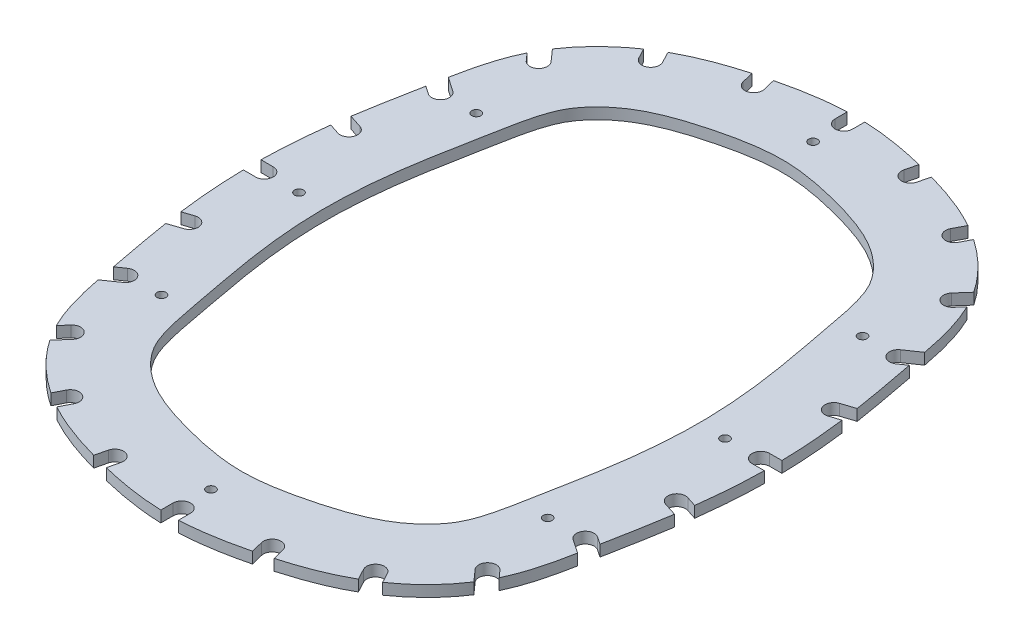
SolidWorks part; units mm, degrees
ref_plane "Front Plane" through (0, 0, 0) normal (0, 0, 1) x (1, 0, 0)
ref_plane "Top Plane" through (0, 0, 0) normal (0, 1, 0) x (1, 0, 0)
ref_plane "Right Plane" through (0, 0, 0) normal (1, 0, 0) x (0, 0, -1)
sketch "MainControlPoints" plane through (0, 0, 0) normal (0, 1, 0) x (1, 0, 0)
  line L1 (0, 188.5) -> (0, 0) construction
  line L2 (-44.5, 181.8105) -> (44.5, 181.8105) construction
  line L9 (-141, 0) -> (141, 0) construction
  line L10 (-86.25, 165.0195) -> (86.25, 165.0195) construction
  line L11 (-117.5, 132.6399) -> (117.5, 132.6399) construction
  line L12 (-130, 89.4108) -> (130, 89.4108) construction
  line L13 (-137.75, 45.0832) -> (137.75, 45.0832) construction
  spline S0 degree 3 poles (-44.8235, 182.8439) (0, 191.3281) (44.8235, 182.8439) (87.706, 168.1591) (121.8523, 134.6364) (129.8847, 89.1344) (138.6218, 45.2258) (142.1917, 0) (138.6218, -45.2258) (129.8847, -89.1344) (121.8523, -134.6364) (87.706, -168.1591) (44.8235, -182.8439) (0, -191.3281) (-44.8235, -182.8439) (-87.706, -168.1591) (-121.8523, -134.6364) (-129.8847, -89.1344) (-138.6218, -45.2258) (-142.1917, 0) (-138.6218, 45.2258) (-129.8847, 89.1344) (-121.8523, 134.6364) (-87.706, 168.1591) (-44.8235, 182.8439) (0, 191.3281) (44.8235, 182.8439) knots -0.124907 -0.083272 -0.041636 0 0.041636 0.083272 0.124907 0.166543 0.208179 0.25 0.291821 0.333457 0.375093 0.416728 0.458364 0.5 0.541636 0.583272 0.624907 0.666543 0.708179 0.75 0.791821 0.833457 0.875093 0.916728 0.958364 1 1.041636 1.083272 1.124907 only from (0, 188.5) to (0, 188.5)
  point P4 (0, 181.8105)
  point P7 (0, 0)
  point P8 (141, 0)
  point P9 (-141, 0)
  point P11 (44.5, 181.8105)
  point P14 (86.25, 165.0195)
  point P15 (0, 165.0195)
  point P16 (117.5, 132.6399)
  point P17 (130, 89.4108)
  point P18 (-44.5, 181.8105)
  point P19 (-86.25, 165.0195)
  point P20 (-117.5, 132.6399)
  point P23 (0, 132.6399)
  point P24 (137.75, 45.0832)
  point P25 (-130, 89.4108)
  point P26 (-137.75, 45.0832)
  point P27 (0, 188.5)
  point P30 (0, 89.4108)
  point P33 (0, 45.0832)
  point P34 (137.75, -45.0832)
  point P35 (130, -89.4108)
  point P36 (117.5, -132.6399)
  point P37 (86.25, -165.0195)
  point P38 (44.5, -181.8105)
  point P39 (0, -188.5)
  point P40 (-44.5, -181.8105)
  point P41 (-86.25, -165.0195)
  point P42 (-117.5, -132.6399)
  point P43 (-130, -89.4108)
  point P44 (-137.75, -45.0832)
  dimension "D3" = 282
  dimension "D2" = 188.5
  dimension "D5" = 45
  dimension "D6" = 45
  dimension "D1" = 89
  dimension "D4" = 172.5
  dimension "D7" = 45
  dimension "D8" = 235
  dimension "D9" = 45
  dimension "D10" = 260
  dimension "D11" = 45
  dimension "D12" = 275.5
ref_axis "Axis1" through (0, 0, -188.5) along (0, 1, 0)
ref_axis "Axis2" through (44.5, 0, -181.8105) along (0, 1, 0)
ref_axis "Axis3" through (86.25, 0, -165.0195) along (0, 1, 0)
ref_axis "Axis4" through (117.5, 0, -132.6399) along (0, 1, 0)
ref_axis "Axis5" through (130, 0, -89.4108) along (0, 1, 0)
ref_axis "Axis6" through (137.75, 0, -45.0832) along (0, 1, 0)
ref_axis "Axis7" through (141, 0, 0) along (0, 1, 0)
ref_axis "Axis8" through (137.75, 0, 45.0832) along (0, 1, 0)
ref_axis "Axis9" through (130, 0, 89.4108) along (0, 1, 0)
ref_axis "Axis10" through (117.5, 0, 132.6399) along (0, 1, 0)
ref_axis "Axis11" through (86.25, 0, 165.0195) along (0, 1, 0)
ref_axis "Axis12" through (44.5, 0, 181.8105) along (0, 1, 0)
ref_axis "Axis13" through (0, 0, 188.5) along (0, 1, 0)
ref_axis "Axis14" through (-44.5, 0, 181.8105) along (0, 1, 0)
ref_axis "Axis15" through (-86.25, 0, 165.0195) along (0, 1, 0)
ref_axis "Axis16" through (-117.5, 0, 132.6399) along (0, 1, 0)
ref_axis "Axis17" through (-130, 0, 89.4108) along (0, 1, 0)
ref_axis "Axis18" through (-137.75, 0, 45.0832) along (0, 1, 0)
ref_axis "Axis19" through (-141, 0, 0) along (0, 1, 0)
ref_axis "Axis20" through (-137.75, 0, -45.0832) along (0, 1, 0)
ref_axis "Axis21" through (-130, 0, -89.4108) along (0, 1, 0)
ref_axis "Axis22" through (-117.5, 0, -132.6399) along (0, 1, 0)
ref_axis "Axis23" through (-86.25, 0, -165.0195) along (0, 1, 0)
ref_axis "Axis24" through (-44.5, 0, -181.8105) along (0, 1, 0)
sketch "Sketch3" plane through (0, 0, 0) normal (0, 1, 0) x (1, 0, 0)
  spline S2 degree 3 poles (44.8235, 182.8439) (0, 191.3281) (-44.8235, 182.8439) (-87.706, 168.1591) (-121.8523, 134.6364) (-129.8847, 89.1344) (-138.6218, 45.2258) (-142.1917, 0) (-138.6218, -45.2258) (-129.8847, -89.1344) (-121.8523, -134.6364) (-87.706, -168.1591) (-44.8235, -182.8439) (0, -191.3281) (44.8235, -182.8439) (87.706, -168.1591) (121.8523, -134.6364) (129.8847, -89.1344) (138.6218, -45.2258) (142.1917, 0) (138.6218, 45.2258) (129.8847, 89.1344) (121.8523, 134.6364) (87.706, 168.1591) (44.8235, 182.8439) (0, 191.3281) (-44.8235, 182.8439) knots -0.124907 -0.083272 -0.041636 0 0.041636 0.083272 0.124907 0.166543 0.208179 0.25 0.291821 0.333457 0.375093 0.416728 0.458364 0.5 0.541636 0.583272 0.624907 0.666543 0.708179 0.75 0.791821 0.833457 0.875093 0.916728 0.958364 1 1.041636 1.083272 1.124907 only from (0, 188.5) to (0, 188.5)
  spline S3 degree 3 poles (44.8235, 182.8439) (0, 191.3281) (-44.8235, 182.8439) (-87.706, 168.1591) (-121.8523, 134.6364) (-129.8847, 89.1344) (-138.6218, 45.2258) (-142.1917, 0) (-138.6218, -45.2258) (-129.8847, -89.1344) (-121.8523, -134.6364) (-87.706, -168.1591) (-44.8235, -182.8439) (0, -191.3281) (44.8235, -182.8439) (87.706, -168.1591) (121.8523, -134.6364) (129.8847, -89.1344) (138.6218, -45.2258) (142.1917, 0) (138.6218, 45.2258) (129.8847, 89.1344) (121.8523, 134.6364) (87.706, 168.1591) (44.8235, 182.8439) (0, 191.3281) (-44.8235, 182.8439) knots -0.124907 -0.083272 -0.041636 0 0.041636 0.083272 0.124907 0.166543 0.208179 0.25 0.291821 0.333457 0.375093 0.416728 0.458364 0.5 0.541636 0.583272 0.624907 0.666543 0.708179 0.75 0.791821 0.833457 0.875093 0.916728 0.958364 1 1.041636 1.083272 1.124907 only from (0, 188.5) to (0, 188.5)
  dimension "D1" = 0
extrude "MainBody" add sketch "Sketch3" along normal blind 6.35
sketch "Sketch13" plane through (0, 6.35, 0) normal (0, 1, 0) x (1, 0, 0)
  spline S2 degree 3 poles (-0.0923, -195.5) (5.9061, -195.5) (11.7392, -195.085) (23.2981, -193.6453) (29.0237, -192.6199) (37.5559, -190.7615) (40.3905, -190.0886) (46.0447, -188.657) (48.8649, -187.9023) (53.0829, -186.6998) (54.4867, -186.2866) (57.2893, -185.4316) (58.6882, -184.9896) (62.8604, -183.6197) (65.6138, -182.6462) (73.7714, -179.5048) (79.0728, -177.1157) (86.7462, -172.933) (89.2575, -171.4385) (92.9463, -169.029) (94.1653, -168.1965) (96.5575, -166.4889) (97.7326, -165.6128) (101.1944, -162.9177) (103.4182, -161.032) (107.6923, -157.0772) (109.7427, -155.0081) (112.678, -151.7562) (113.633, -150.6474) (115.0284, -148.9451) (115.4873, -148.3711) (116.3925, -147.2097) (116.8393, -146.6213) (119.0306, -143.6582) (120.6466, -141.2209) (123.5916, -136.206) (124.9153, -133.6259) (127.2923, -128.3337) (128.3485, -125.623) (129.7723, -121.4785) (130.2202, -120.084) (131.0691, -117.272) (131.4694, -115.8571) (132.6042, -111.6095) (133.2755, -108.7656) (134.5145, -103.0626) (135.0819, -100.2036) (136.1775, -94.48) (136.707, -91.6156) (138.3251, -83.0265) (139.4215, -77.303) (141.5293, -65.8438) (142.5403, -60.108) (143.9035, -51.4821) (144.3323, -48.6031) (145.1247, -42.8358) (145.4885, -39.9475) (147.1362, -25.4811) (147.9101, -13.8294) (148.003, -0.6092) (148.0024, 0.8623) (147.9792, 3.8019) (147.9568, 5.2701) (147.8578, 9.6699) (147.7498, 12.5969) (147.3068, 21.3604) (146.8533, 27.1792) (145.6651, 38.7754) (144.9284, 44.5524) (143.2126, 56.0705) (142.2389, 61.8124) (140.1775, 73.2794) (139.0901, 79.0044) (137.4645, 87.5929) (136.9262, 90.4562) (135.8531, 96.1835) (135.3122, 99.0464) (133.5786, 107.6189) (132.2779, 113.3124) (130.1353, 120.3529) (129.6824, 121.7514) (128.7233, 124.5187) (128.2169, 125.8886) (126.6073, 129.9525) (125.4138, 132.6004) (122.7385, 137.7496) (121.2544, 140.2496) (118.8215, 143.8945) (117.9761, 145.0919) (116.2177, 147.4523) (115.3033, 148.6168) (112.4942, 152.0199) (110.5242, 154.1827) (106.4077, 158.3162) (104.2612, 160.2869) (99.8013, 164.0465) (97.4878, 165.8355) (93.8939, 168.384) (92.6724, 169.2128) (90.2027, 170.8151) (88.9554, 171.5879) (82.6598, 175.3171) (77.4348, 177.8708) (66.7035, 182.3362) (61.1969, 184.2476) (54.1978, 186.3725) (52.791, 186.7846) (49.9736, 187.5842) (48.5634, 187.9716) (44.3294, 189.1029) (41.5021, 189.818) (33.0032, 191.8167) (27.3144, 192.953) (15.8708, 194.6608) (10.1162, 195.2328) (1.4182, 195.5241) (-1.4925, 195.5238) (-7.3372, 195.3237) (-10.2708, 195.1267) (-14.6866, 194.6996) (-16.1609, 194.5352) (-19.0943, 194.1679) (-20.556, 193.9647) (-24.9277, 193.3015) (-27.824, 192.7881) (-36.4681, 191.071) (-42.1715, 189.6926) (-53.5026, 186.6371) (-59.1262, 184.9441) (-66.0624, 182.4605) (-67.445, 181.9454) (-70.1997, 180.8739) (-71.5737, 180.3168) (-75.6639, 178.5832) (-78.3432, 177.3468) (-83.5935, 174.6901) (-86.1644, 173.2698) (-91.1858, 170.2243) (-93.6357, 168.5985) (-97.2169, 166.0005) (-98.395, 165.108) (-100.7189, 163.2682) (-101.8655, 162.32) (-105.2234, 159.4186) (-107.3637, 157.4004) (-111.4418, 153.191) (-113.3796, 150.9998) (-117.0378, 146.4319) (-118.7583, 144.0551) (-121.1568, 140.3344) (-121.9259, 139.0681) (-123.0304, 137.1268) (-123.3898, 136.4736) (-124.087, 135.1618) (-124.4255, 134.5022) (-126.0692, 131.1868) (-127.2294, 128.4785) (-130.3408, 120.2205) (-131.9223, 114.5371) (-134.5909, 102.9918) (-135.6643, 97.1921) (-137.8355, 85.5987) (-138.9477, 79.8043) (-141.1029, 68.2094) (-142.1451, 62.4088) (-143.5618, 53.6948) (-144.0097, 50.788) (-144.8419, 44.9686) (-145.2255, 42.056) (-146.97, 27.4776) (-147.815, 15.7657) (-148.0521, -1.8942) (-147.9538, -7.7967) (-147.4225, -19.6316) (-146.9909, -25.5639) (-146.1143, -34.4827) (-145.7838, -37.4592) (-145.0527, -43.3941) (-144.6515, -46.3556) (-143.3516, -55.2244) (-142.36, -61.1163) (-140.253, -72.8796) (-139.1381, -78.7512) (-137.4708, -87.5593) (-136.9189, -90.496) (-135.8181, -96.3698) (-135.2627, -99.3053) (-133.4794, -108.0788) (-132.1352, -113.8842) (-129.4893, -122.4151) (-128.5024, -125.2292) (-126.8117, -129.3912) (-126.2131, -130.7686) (-125.2553, -132.818) (-124.9263, -133.498) (-124.2516, -134.843) (-123.9056, -135.5092) (-122.1306, -138.8075) (-120.5688, -141.343) (-117.1925, -146.2303) (-115.378, -148.582) (-111.5149, -153.1153) (-109.4647, -155.2983) (-105.1449, -159.494) (-102.9036, -161.4797) (-95.9543, -167.1259) (-91.0211, -170.4758) (-84.4967, -174.1698) (-83.1716, -174.8856) (-80.5028, -176.2632) (-79.1594, -176.925) (-75.1047, -178.8358) (-72.3686, -180.0105) (-64.0786, -183.2871) (-58.4429, -185.1422) (-49.8888, -187.6214) (-47.0211, -188.3984) (-41.2605, -189.8765) (-38.3664, -190.5739) (-32.5429, -191.862) (-29.6099, -192.4531) (-23.735, -193.4975) (-20.7901, -193.9515) (-14.8831, -194.699) (-11.9208, -194.9924) (-7.4624, -195.2928) (-5.9738, -195.3696) (-3.7367, -195.4473) (-2.6172, -195.4768) (-1.3092, -195.4942) (-0.6548, -195.4985) (-0.3742, -195.4995) (-0.1871, -195.4999) (-0.0923, -195.5) (5.9061, -195.5) (11.7392, -195.085) knots -0.000244 -0.000244 0 0 0.015625 0.015625 0.03125 0.03125 0.039063 0.039063 0.046875 0.046875 0.050781 0.050781 0.054688 0.054688 0.0625 0.0625 0.078125 0.078125 0.085938 0.085938 0.089844 0.089844 0.09375 0.09375 0.101563 0.101563 0.109375 0.109375 0.113281 0.113281 0.115234 0.115234 0.117188 0.117188 0.125 0.125 0.132813 0.132813 0.140625 0.140625 0.144531 0.144531 0.148438 0.148438 0.15625 0.15625 0.164063 0.164063 0.171875 0.171875 0.1875 0.1875 0.203125 0.203125 0.210938 0.210938 0.21875 0.21875 0.25 0.25 0.253906 0.253906 0.257813 0.257813 0.265625 0.265625 0.28125 0.28125 0.296875 0.296875 0.3125 0.3125 0.328125 0.328125 0.335938 0.335938 0.34375 0.34375 0.359375 0.359375 0.363281 0.363281 0.367188 0.367188 0.375 0.375 0.382813 0.382813 0.386719 0.386719 0.390625 0.390625 0.398438 0.398438 0.40625 0.40625 0.414063 0.414063 0.417969 0.417969 0.421875 0.421875 0.4375 0.4375 0.453125 0.453125 0.457031 0.457031 0.460938 0.460938 0.46875 0.46875 0.484375 0.484375 0.5 0.5 0.507813 0.507813 0.515625 0.515625 0.519531 0.519531 0.523438 0.523438 0.53125 0.53125 0.546875 0.546875 0.5625 0.5625 0.566406 0.566406 0.570313 0.570313 0.578125 0.578125 0.585938 0.585938 0.59375 0.59375 0.597656 0.597656 0.601563 0.601563 0.609375 0.609375 0.617188 0.617188 0.625 0.625 0.628906 0.628906 0.630859 0.630859 0.632813 0.632813 0.640625 0.640625 0.65625 0.65625 0.671875 0.671875 0.6875 0.6875 0.703125 0.703125 0.710937 0.710937 0.71875 0.71875 0.75 0.75 0.765625 0.765625 0.78125 0.78125 0.789062 0.789062 0.796875 0.796875 0.8125 0.8125 0.828125 0.828125 0.835937 0.835937 0.84375 0.84375 0.859375 0.859375 0.867187 0.867187 0.871094 0.871094 0.873047 0.873047 0.875 0.875 0.882812 0.882812 0.890625 0.890625 0.898437 0.898437 0.90625 0.90625 0.921875 0.921875 0.925781 0.925781 0.929687 0.929687 0.9375 0.9375 0.953125 0.953125 0.960937 0.960937 0.96875 0.96875 0.976562 0.976562 0.984375 0.984375 0.992188 0.992188 0.996094 0.996094 0.998047 0.999023 0.999512 0.999756 0.999756 1 1 1.015625 1.015625 1.03125 only from (0, -195.5) to (0, -195.5)
  spline S3 degree 3 poles (-0.0923, -195.5) (5.9061, -195.5) (11.7392, -195.085) (23.2981, -193.6453) (29.0237, -192.6199) (37.5559, -190.7615) (40.3905, -190.0886) (46.0447, -188.657) (48.8649, -187.9023) (53.0829, -186.6998) (54.4867, -186.2866) (57.2893, -185.4316) (58.6882, -184.9896) (62.8604, -183.6197) (65.6138, -182.6462) (73.7714, -179.5048) (79.0728, -177.1157) (86.7462, -172.933) (89.2575, -171.4385) (92.9463, -169.029) (94.1653, -168.1965) (96.5575, -166.4889) (97.7326, -165.6128) (101.1944, -162.9177) (103.4182, -161.032) (107.6923, -157.0772) (109.7427, -155.0081) (112.678, -151.7562) (113.633, -150.6474) (115.0284, -148.9451) (115.4873, -148.3711) (116.3925, -147.2097) (116.8393, -146.6213) (119.0306, -143.6582) (120.6466, -141.2209) (123.5916, -136.206) (124.9153, -133.6259) (127.2923, -128.3337) (128.3485, -125.623) (129.7723, -121.4785) (130.2202, -120.084) (131.0691, -117.272) (131.4694, -115.8571) (132.6042, -111.6095) (133.2755, -108.7656) (134.5145, -103.0626) (135.0819, -100.2036) (136.1775, -94.48) (136.707, -91.6156) (138.3251, -83.0265) (139.4215, -77.303) (141.5293, -65.8438) (142.5403, -60.108) (143.9035, -51.4821) (144.3323, -48.6031) (145.1247, -42.8358) (145.4885, -39.9475) (147.1362, -25.4811) (147.9101, -13.8294) (148.003, -0.6092) (148.0024, 0.8623) (147.9792, 3.8019) (147.9568, 5.2701) (147.8578, 9.6699) (147.7498, 12.5969) (147.3068, 21.3604) (146.8533, 27.1792) (145.6651, 38.7754) (144.9284, 44.5524) (143.2126, 56.0705) (142.2389, 61.8124) (140.1775, 73.2794) (139.0901, 79.0044) (137.4645, 87.5929) (136.9262, 90.4562) (135.8531, 96.1835) (135.3122, 99.0464) (133.5786, 107.6189) (132.2779, 113.3124) (130.1353, 120.3529) (129.6824, 121.7514) (128.7233, 124.5187) (128.2169, 125.8886) (126.6073, 129.9525) (125.4138, 132.6004) (122.7385, 137.7496) (121.2544, 140.2496) (118.8215, 143.8945) (117.9761, 145.0919) (116.2177, 147.4523) (115.3033, 148.6168) (112.4942, 152.0199) (110.5242, 154.1827) (106.4077, 158.3162) (104.2612, 160.2869) (99.8013, 164.0465) (97.4878, 165.8355) (93.8939, 168.384) (92.6724, 169.2128) (90.2027, 170.8151) (88.9554, 171.5879) (82.6598, 175.3171) (77.4348, 177.8708) (66.7035, 182.3362) (61.1969, 184.2476) (54.1978, 186.3725) (52.791, 186.7846) (49.9736, 187.5842) (48.5634, 187.9716) (44.3294, 189.1029) (41.5021, 189.818) (33.0032, 191.8167) (27.3144, 192.953) (15.8708, 194.6608) (10.1162, 195.2328) (1.4182, 195.5241) (-1.4925, 195.5238) (-7.3372, 195.3237) (-10.2708, 195.1267) (-14.6866, 194.6996) (-16.1609, 194.5352) (-19.0943, 194.1679) (-20.556, 193.9647) (-24.9277, 193.3015) (-27.824, 192.7881) (-36.4681, 191.071) (-42.1715, 189.6926) (-53.5026, 186.6371) (-59.1262, 184.9441) (-66.0624, 182.4605) (-67.445, 181.9454) (-70.1997, 180.8739) (-71.5737, 180.3168) (-75.6639, 178.5832) (-78.3432, 177.3468) (-83.5935, 174.6901) (-86.1644, 173.2698) (-91.1858, 170.2243) (-93.6357, 168.5985) (-97.2169, 166.0005) (-98.395, 165.108) (-100.7189, 163.2682) (-101.8655, 162.32) (-105.2234, 159.4186) (-107.3637, 157.4004) (-111.4418, 153.191) (-113.3796, 150.9998) (-117.0378, 146.4319) (-118.7583, 144.0551) (-121.1568, 140.3344) (-121.9259, 139.0681) (-123.0304, 137.1268) (-123.3898, 136.4736) (-124.087, 135.1618) (-124.4255, 134.5022) (-126.0692, 131.1868) (-127.2294, 128.4785) (-130.3408, 120.2205) (-131.9223, 114.5371) (-134.5909, 102.9918) (-135.6643, 97.1921) (-137.8355, 85.5987) (-138.9477, 79.8043) (-141.1029, 68.2094) (-142.1451, 62.4088) (-143.5618, 53.6948) (-144.0097, 50.788) (-144.8419, 44.9686) (-145.2255, 42.056) (-146.97, 27.4776) (-147.815, 15.7657) (-148.0521, -1.8942) (-147.9538, -7.7967) (-147.4225, -19.6316) (-146.9909, -25.5639) (-146.1143, -34.4827) (-145.7838, -37.4592) (-145.0527, -43.3941) (-144.6515, -46.3556) (-143.3516, -55.2244) (-142.36, -61.1163) (-140.253, -72.8796) (-139.1381, -78.7512) (-137.4708, -87.5593) (-136.9189, -90.496) (-135.8181, -96.3698) (-135.2627, -99.3053) (-133.4794, -108.0788) (-132.1352, -113.8842) (-129.4893, -122.4151) (-128.5024, -125.2292) (-126.8117, -129.3912) (-126.2131, -130.7686) (-125.2553, -132.818) (-124.9263, -133.498) (-124.2516, -134.843) (-123.9056, -135.5092) (-122.1306, -138.8075) (-120.5688, -141.343) (-117.1925, -146.2303) (-115.378, -148.582) (-111.5149, -153.1153) (-109.4647, -155.2983) (-105.1449, -159.494) (-102.9036, -161.4797) (-95.9543, -167.1259) (-91.0211, -170.4758) (-84.4967, -174.1698) (-83.1716, -174.8856) (-80.5028, -176.2632) (-79.1594, -176.925) (-75.1047, -178.8358) (-72.3686, -180.0105) (-64.0786, -183.2871) (-58.4429, -185.1422) (-49.8888, -187.6214) (-47.0211, -188.3984) (-41.2605, -189.8765) (-38.3664, -190.5739) (-32.5429, -191.862) (-29.6099, -192.4531) (-23.735, -193.4975) (-20.7901, -193.9515) (-14.8831, -194.699) (-11.9208, -194.9924) (-7.4624, -195.2928) (-5.9738, -195.3696) (-3.7367, -195.4473) (-2.6172, -195.4768) (-1.3092, -195.4942) (-0.6548, -195.4985) (-0.3742, -195.4995) (-0.1871, -195.4999) (-0.0923, -195.5) (5.9061, -195.5) (11.7392, -195.085) knots -0.000244 -0.000244 0 0 0.015625 0.015625 0.03125 0.03125 0.039063 0.039063 0.046875 0.046875 0.050781 0.050781 0.054688 0.054688 0.0625 0.0625 0.078125 0.078125 0.085938 0.085938 0.089844 0.089844 0.09375 0.09375 0.101563 0.101563 0.109375 0.109375 0.113281 0.113281 0.115234 0.115234 0.117188 0.117188 0.125 0.125 0.132813 0.132813 0.140625 0.140625 0.144531 0.144531 0.148438 0.148438 0.15625 0.15625 0.164063 0.164063 0.171875 0.171875 0.1875 0.1875 0.203125 0.203125 0.210938 0.210938 0.21875 0.21875 0.25 0.25 0.253906 0.253906 0.257813 0.257813 0.265625 0.265625 0.28125 0.28125 0.296875 0.296875 0.3125 0.3125 0.328125 0.328125 0.335938 0.335938 0.34375 0.34375 0.359375 0.359375 0.363281 0.363281 0.367188 0.367188 0.375 0.375 0.382813 0.382813 0.386719 0.386719 0.390625 0.390625 0.398438 0.398438 0.40625 0.40625 0.414063 0.414063 0.417969 0.417969 0.421875 0.421875 0.4375 0.4375 0.453125 0.453125 0.457031 0.457031 0.460938 0.460938 0.46875 0.46875 0.484375 0.484375 0.5 0.5 0.507813 0.507813 0.515625 0.515625 0.519531 0.519531 0.523438 0.523438 0.53125 0.53125 0.546875 0.546875 0.5625 0.5625 0.566406 0.566406 0.570313 0.570313 0.578125 0.578125 0.585938 0.585938 0.59375 0.59375 0.597656 0.597656 0.601563 0.601563 0.609375 0.609375 0.617188 0.617188 0.625 0.625 0.628906 0.628906 0.630859 0.630859 0.632813 0.632813 0.640625 0.640625 0.65625 0.65625 0.671875 0.671875 0.6875 0.6875 0.703125 0.703125 0.710937 0.710937 0.71875 0.71875 0.75 0.75 0.765625 0.765625 0.78125 0.78125 0.789062 0.789062 0.796875 0.796875 0.8125 0.8125 0.828125 0.828125 0.835937 0.835937 0.84375 0.84375 0.859375 0.859375 0.867187 0.867187 0.871094 0.871094 0.873047 0.873047 0.875 0.875 0.882812 0.882812 0.890625 0.890625 0.898437 0.898437 0.90625 0.90625 0.921875 0.921875 0.925781 0.925781 0.929687 0.929687 0.9375 0.9375 0.953125 0.953125 0.960937 0.960937 0.96875 0.96875 0.976562 0.976562 0.984375 0.984375 0.992188 0.992188 0.996094 0.996094 0.998047 0.999023 0.999512 0.999756 0.999756 1 1 1.015625 1.015625 1.03125 only from (0, -195.5) to (0, -195.5)
  dimension "D1" = 7
extrude "Extrude2Lip" add sketch "Sketch13" against normal up to surface (6.35 mm away)
sketch "Sketch14" plane through (0, 6.35, 0) normal (0, 1, 0) x (1, 0, 0)
  line L0 (-5, 188.5) -> (-5, 199.1798)
  line L1 (-5, 199.1798) -> (5, 199.1798)
  line L2 (5, 199.1798) -> (5, 188.5)
  line L9 (0, 188.5) -> (0, 199.1798) construction
  line L13 (-5, 188.5) -> (5, 188.5) construction
  line L20 (39.6434, 182.9992) -> (42.1824, 193.3728)
  line L21 (42.1824, 193.3728) -> (51.8957, 190.9953)
  line L22 (0, 0) -> (44.5, 181.8105) construction
  line L23 (0, 0) -> (86.25, 165.0195) construction
  line L24 (0, 0) -> (117.5, 132.6399) construction
  line L25 (0, 0) -> (130, 89.4108) construction
  line L26 (0, 0) -> (137.75, 45.0832) construction
  line L27 (0, 0) -> (141, 0.3435) construction
  line L28 (0, 0) -> (0, 188.5) construction
  line L29 (51.8957, 190.9953) -> (49.3566, 180.6217)
  line L30 (44.5, 181.8105) -> (47.039, 192.1841) construction
  line L31 (39.6434, 182.9992) -> (49.3566, 180.6217) construction
  line L32 (81.8188, 167.3355) -> (86.7658, 176.8005)
  line L33 (86.7658, 176.8005) -> (95.6283, 172.1684)
  line L34 (95.6283, 172.1684) -> (90.6812, 162.7034)
  line L35 (86.25, 165.0195) -> (91.197, 174.4844) construction
  line L36 (81.8188, 167.3355) -> (90.6812, 162.7034) construction
  line L37 (113.7573, 135.9554) -> (125.8891, 149.6503)
  line L38 (125.8891, 149.6503) -> (133.3744, 143.0193)
  line L39 (133.3744, 143.0193) -> (121.2427, 129.3244)
  line L40 (117.5, 132.6399) -> (129.6317, 146.3348) construction
  line L41 (113.7573, 135.9554) -> (121.2427, 129.3244) construction
  line L42 (127.1666, 93.5305) -> (142.2527, 103.9064)
  line L43 (142.2527, 103.9064) -> (147.9195, 95.667)
  line L44 (147.9195, 95.667) -> (132.8334, 85.2912)
  line L45 (130, 89.4108) -> (145.0861, 99.7867) construction
  line L46 (127.1666, 93.5305) -> (132.8334, 85.2912) construction
  line L47 (136.1948, 49.8352) -> (153.5963, 55.5304)
  line L48 (153.5963, 55.5304) -> (156.7067, 46.0265)
  line L49 (156.7067, 46.0265) -> (139.3052, 40.3312)
  line L50 (137.75, 45.0832) -> (155.1515, 50.7784) construction
  line L51 (136.1948, 49.8352) -> (139.3052, 40.3312) construction
  line L52 (140.9878, 5.3435) -> (159.2975, 5.3881)
  line L53 (159.2975, 5.3881) -> (159.3219, -4.6119)
  line L54 (159.3219, -4.6119) -> (141.0122, -4.6565)
  line L55 (141, 0.3435) -> (159.3097, 0.3881) construction
  line L56 (140.9878, 5.3435) -> (141.0122, -4.6565) construction
  line L57 (-140.9878, 5.3435) -> (-141.0122, -4.6565) construction
  line L58 (-141, 0.3435) -> (-159.3097, 0.3881) construction
  line L59 (-136.1948, 49.8352) -> (-139.3052, 40.3312) construction
  line L60 (-137.75, 45.0832) -> (-155.1515, 50.7784) construction
  line L61 (-127.1666, 93.5305) -> (-132.8334, 85.2912) construction
  line L62 (-130, 89.4108) -> (-145.0861, 99.7867) construction
  line L63 (-113.7573, 135.9554) -> (-121.2427, 129.3244) construction
  line L64 (-117.5, 132.6399) -> (-129.6317, 146.3348) construction
  line L65 (-81.8188, 167.3355) -> (-90.6812, 162.7034) construction
  line L66 (-86.25, 165.0195) -> (-91.197, 174.4844) construction
  line L67 (-39.6434, 182.9992) -> (-49.3566, 180.6217) construction
  line L68 (-44.5, 181.8105) -> (-47.039, 192.1841) construction
  line L69 (-159.3219, -4.6119) -> (-141.0122, -4.6565)
  line L70 (-159.2975, 5.3881) -> (-159.3219, -4.6119)
  line L71 (-140.9878, 5.3435) -> (-159.2975, 5.3881)
  line L72 (-156.7067, 46.0265) -> (-139.3052, 40.3312)
  line L73 (-153.5963, 55.5304) -> (-156.7067, 46.0265)
  line L74 (-136.1948, 49.8352) -> (-153.5963, 55.5304)
  line L75 (-147.9195, 95.667) -> (-132.8334, 85.2912)
  line L76 (-142.2527, 103.9064) -> (-147.9195, 95.667)
  line L77 (-127.1666, 93.5305) -> (-142.2527, 103.9064)
  line L78 (-133.3744, 143.0193) -> (-121.2427, 129.3244)
  line L79 (-125.8891, 149.6503) -> (-133.3744, 143.0193)
  line L80 (-113.7573, 135.9554) -> (-125.8891, 149.6503)
  line L81 (-95.6283, 172.1684) -> (-90.6812, 162.7034)
  line L82 (-86.7658, 176.8005) -> (-95.6283, 172.1684)
  line L83 (-81.8188, 167.3355) -> (-86.7658, 176.8005)
  line L84 (-51.8957, 190.9953) -> (-49.3566, 180.6217)
  line L85 (-42.1824, 193.3728) -> (-51.8957, 190.9953)
  line L86 (-39.6434, 182.9992) -> (-42.1824, 193.3728)
  line L87 (-43.6136, -182.0251) -> (-46.1021, -192.411) construction
  line L88 (-38.7512, -183.1902) -> (-48.476, -180.8601) construction
  line L89 (-85.4449, -165.4378) -> (-90.3457, -174.9267) construction
  line L90 (-81.0024, -167.7322) -> (-89.8874, -163.1433) construction
  line L91 (-116.8523, -133.2108) -> (-128.9172, -146.9647) construction
  line L92 (-113.0935, -136.508) -> (-120.6111, -129.9136) construction
  line L93 (-129.5628, -90.0432) -> (-144.5981, -100.4924) construction
  line L94 (-126.7093, -94.149) -> (-132.4163, -85.9374) construction
  line L95 (-137.5287, -45.7539) -> (-154.9022, -51.5338) construction
  line L96 (-135.9503, -50.4982) -> (-139.1071, -41.0095) construction
  line L97 (136.436, -49.171) -> (139.5001, -39.652) construction
  line L98 (137.968, -44.4115) -> (155.3971, -50.0219) construction
  line L99 (127.6208, -92.9098) -> (133.2474, -84.6429) construction
  line L100 (130.4341, -88.7763) -> (145.5706, -99.0786) construction
  line L101 (114.4184, -135.3995) -> (121.8714, -128.7321) construction
  line L102 (118.1449, -132.0658) -> (130.3432, -145.7014) construction
  line L103 (82.6331, -166.9349) -> (91.4729, -162.2596) construction
  line L104 (87.053, -164.5972) -> (92.0461, -174.038) construction
  line L105 (40.5346, -182.8038) -> (50.2361, -180.3791) construction
  line L106 (45.3853, -181.5915) -> (47.9749, -191.9526) construction
  line L107 (-4.0815, -188.5221) -> (5.9184, -188.4734) construction
  line L108 (0.9185, -188.4978) -> (0.9705, -199.1775) construction
  line L109 (-38.7512, -183.1902) -> (-41.2397, -193.576)
  line L110 (-41.2397, -193.576) -> (-50.9644, -191.2459)
  line L111 (-50.9644, -191.2459) -> (-48.476, -180.8601)
  line L112 (-81.0024, -167.7322) -> (-85.9033, -177.2212)
  line L113 (-85.9033, -177.2212) -> (-94.7882, -172.6323)
  line L114 (-94.7882, -172.6323) -> (-89.8874, -163.1433)
  line L115 (-113.0935, -136.508) -> (-125.1584, -150.2619)
  line L116 (-125.1584, -150.2619) -> (-132.676, -143.6675)
  line L117 (-132.676, -143.6675) -> (-120.6111, -129.9136)
  line L118 (-126.7093, -94.149) -> (-141.7447, -104.5983)
  line L119 (-141.7447, -104.5983) -> (-147.4516, -96.3866)
  line L120 (-147.4516, -96.3866) -> (-132.4163, -85.9374)
  line L121 (-135.9503, -50.4982) -> (-153.3239, -56.2781)
  line L122 (-153.3239, -56.2781) -> (-156.4806, -46.7895)
  line L123 (-156.4806, -46.7895) -> (-139.1071, -41.0095)
  line L124 (156.9292, -45.2624) -> (139.5001, -39.652)
  line L125 (153.865, -54.7813) -> (156.9292, -45.2624)
  line L126 (136.436, -49.171) -> (153.865, -54.7813)
  line L127 (148.3839, -94.9451) -> (133.2474, -84.6429)
  line L128 (142.7573, -103.212) -> (148.3839, -94.9451)
  line L129 (127.6208, -92.9098) -> (142.7573, -103.212)
  line L130 (134.0697, -142.3677) -> (121.8714, -128.7321)
  line L131 (126.6167, -149.0351) -> (134.0697, -142.3677)
  line L132 (114.4184, -135.3995) -> (126.6167, -149.0351)
  line L133 (96.466, -171.7004) -> (91.4729, -162.2596)
  line L134 (87.6262, -176.3756) -> (96.466, -171.7004)
  line L135 (82.6331, -166.9349) -> (87.6262, -176.3756)
  line L136 (52.8257, -190.7402) -> (50.2361, -180.3791)
  line L137 (43.1241, -193.1649) -> (52.8257, -190.7402)
  line L138 (40.5346, -182.8038) -> (43.1241, -193.1649)
  line L139 (5.9704, -199.1531) -> (5.9184, -188.4734)
  line L140 (-4.0294, -199.2018) -> (5.9704, -199.1531)
  line L141 (-4.0815, -188.5221) -> (-4.0294, -199.2018)
  arc A0 (-5, 188.5) -> (5, 188.5) centre (0, 188.5) ccw
  arc A1 (39.6434, 182.9992) -> (49.3566, 180.6217) centre (44.5, 181.8105) ccw
  arc A2 (81.8188, 167.3355) -> (90.6812, 162.7034) centre (86.25, 165.0195) ccw
  arc A3 (113.7573, 135.9554) -> (121.2427, 129.3244) centre (117.5, 132.6399) ccw
  arc A4 (127.1666, 93.5305) -> (132.8334, 85.2912) centre (130, 89.4108) ccw
  arc A5 (136.1948, 49.8352) -> (139.3052, 40.3312) centre (137.75, 45.0832) ccw
  arc A6 (140.9878, 5.3435) -> (141.0122, -4.6565) centre (141, 0.3435) ccw
  arc A7 (-140.9878, 5.3435) -> (-141.0122, -4.6565) centre (-141, 0.3435) cw
  arc A8 (-136.1948, 49.8352) -> (-139.3052, 40.3312) centre (-137.75, 45.0832) cw
  arc A9 (-127.1666, 93.5305) -> (-132.8334, 85.2912) centre (-130, 89.4108) cw
  arc A10 (-113.7573, 135.9554) -> (-121.2427, 129.3244) centre (-117.5, 132.6399) cw
  arc A11 (-81.8188, 167.3355) -> (-90.6812, 162.7034) centre (-86.25, 165.0195) cw
  arc A12 (-39.6434, 182.9992) -> (-49.3566, 180.6217) centre (-44.5, 181.8105) cw
  arc A13 (-38.7512, -183.1902) -> (-48.476, -180.8601) centre (-43.6136, -182.0251) ccw
  arc A14 (-81.0024, -167.7322) -> (-89.8874, -163.1433) centre (-85.4449, -165.4378) ccw
  arc A15 (-113.0935, -136.508) -> (-120.6111, -129.9136) centre (-116.8523, -133.2108) ccw
  arc A16 (-126.7093, -94.149) -> (-132.4163, -85.9374) centre (-129.5628, -90.0432) ccw
  arc A17 (-135.9503, -50.4982) -> (-139.1071, -41.0095) centre (-137.5287, -45.7539) ccw
  arc A18 (136.436, -49.171) -> (139.5001, -39.652) centre (137.968, -44.4115) cw
  arc A19 (127.6208, -92.9098) -> (133.2474, -84.6429) centre (130.4341, -88.7763) cw
  arc A20 (114.4184, -135.3995) -> (121.8714, -128.7321) centre (118.1449, -132.0658) cw
  arc A21 (82.6331, -166.9349) -> (91.4729, -162.2596) centre (87.053, -164.5972) cw
  arc A22 (40.5346, -182.8038) -> (50.2361, -180.3791) centre (45.3853, -181.5915) cw
  arc A23 (-4.0815, -188.5221) -> (5.9184, -188.4734) centre (0.9185, -188.4978) cw
  point P16 (44.5, 181.8105)
  dimension "D1" = 5
  dimension "D4" = 10
extrude "Slots" cut sketch "Sketch14" against normal up to next
ref_plane "MajorAxisPlane" through (0, 0, 0) normal (-1, 0, 0) x (0, 0, 1)
ref_plane "MinorAxisPlane" through (0, 0, 0) normal (0, 0, 1) x (1, 0, 0)
sketch "Sketch16" plane through (0, 6.35, 0) normal (0, 1, 0) x (1, 0, 0)
  spline S2 degree 3 poles (-0.0721, -153.5) (2.3061, -153.5) (4.5951, -153.4048) (9.1461, -153.0645) (11.408, -152.8191) (18.1617, -151.9037) (22.6216, -151.0562) (29.2711, -149.5613) (31.4808, -149.0251) (35.8896, -147.8942) (38.0893, -147.3022) (42.4761, -146.0487) (44.6661, -145.3853) (49.0044, -143.9654) (51.1543, -143.2087) (55.4026, -141.571) (57.501, -140.69) (61.6306, -138.7653) (63.6638, -137.7206) (67.6351, -135.4255) (69.5476, -134.1866) (73.221, -131.5191) (74.9832, -130.0922) (77.5042, -127.799) (78.324, -127.009) (79.5201, -125.7819) (79.9132, -125.3658) (80.6875, -124.5188) (81.0689, -124.0876) (82.9296, -121.9094) (84.2839, -120.085) (86.0662, -117.1966) (86.617, -116.2074) (87.6262, -114.1727) (88.0878, -113.1291) (88.7308, -111.5337) (88.9372, -110.9959) (89.3332, -109.9173) (89.523, -109.3763) (90.0713, -107.7488) (90.4088, -106.6579) (91.3592, -103.3721) (91.9108, -101.1643) (92.9251, -96.7301) (93.3872, -94.5035) (94.2707, -90.0417) (94.6918, -87.8065) (95.5296, -83.3351) (95.9487, -81.0995) (97.2159, -74.3946) (98.0672, -69.9261) (99.7242, -60.9794) (100.5301, -56.4992) (102.0284, -47.524) (102.7189, -43.0363) (103.9132, -34.0603) (104.4198, -29.5721) (105.6413, -16.1068) (106.0587, -7.1289) (105.9278, 10.8292) (105.3913, 19.8094) (104.0068, 33.2811) (103.4477, 37.772) (102.155, 46.7541) (101.4236, 51.2484) (99.8668, 60.22) (99.0416, 64.6971) (97.3625, 73.6462) (96.5085, 78.118) (95.2486, 84.8297) (94.8332, 87.0677) (93.9784, 91.5394) (93.5393, 93.7723) (92.5952, 98.2209) (92.0907, 100.4367) (90.9569, 104.8358) (90.3288, 107.0193) (89.2207, 110.2515) (88.8231, 111.3223) (87.9526, 113.441) (87.484, 114.4785) (85.949, 117.5059) (84.7418, 119.4034) (82.7212, 122.1116) (82.0124, 122.9912) (80.9008, 124.2787) (80.5223, 124.7026) (79.7495, 125.5402) (79.355, 125.9541) (77.3589, 127.9843) (75.6776, 129.4953) (72.1703, 132.3235) (70.344, 133.6403) (67.5002, 135.4756) (66.5345, 136.0636) (64.5697, 137.1948) (63.5685, 137.7394) (60.5359, 139.3039) (58.4849, 140.2511) (54.339, 142.0012) (52.2439, 142.8039) (45.9092, 145.0499) (41.6207, 146.3331) (35.1376, 148.0925) (32.9687, 148.6532) (28.6124, 149.7144) (26.4249, 150.214) (22.0253, 151.1331) (19.8134, 151.5528) (15.3584, 152.2905) (13.1277, 152.6062) (8.6753, 153.1061) (6.4513, 153.2908) (2.0086, 153.503) (-0.2101, 153.5278) (-6.8575, 153.341) (-11.2782, 152.8908) (-17.8984, 151.8877) (-20.1032, 151.4981) (-23.4083, 150.846) (-24.5106, 150.6171) (-26.7086, 150.1404) (-27.8045, 149.8925) (-31.0839, 149.1239) (-33.2592, 148.5781) (-37.593, 147.4355) (-39.7516, 146.8392) (-46.1919, 144.9419) (-50.439, 143.536) (-56.6815, 141.0378) (-58.7408, 140.1395) (-61.7868, 138.6619) (-62.7964, 138.1468) (-64.7929, 137.0701) (-65.7754, 136.5109) (-68.671, 134.7653) (-70.5314, 133.5096) (-74.1096, 130.8103) (-75.8278, 129.3673) (-78.2856, 127.0457) (-79.0849, 126.2455) (-80.2504, 125.0014) (-80.633, 124.5797) (-81.3805, 123.7276) (-81.7461, 123.2964) (-83.5325, 121.114) (-84.8297, 119.2844) (-86.5234, 116.3805) (-87.0426, 115.3837) (-87.999, 113.3383) (-88.4391, 112.2883) (-89.6625, 109.0979) (-90.3433, 106.942) (-91.5587, 102.5989) (-92.0915, 100.4113) (-93.0761, 96.0186) (-93.5274, 93.8135) (-94.3939, 89.3955) (-94.809, 87.1826) (-95.6376, 82.7565) (-96.0535, 80.5438) (-97.3085, 73.9072) (-98.1504, 69.4839) (-99.7878, 60.6275) (-100.5838, 56.1906) (-102.0609, 47.3157) (-102.7414, 42.878) (-103.9195, 34.0022) (-104.4199, 29.564) (-105.6297, 16.2486) (-106.0484, 7.3705) (-105.9426, -10.3886) (-105.4278, -19.2696) (-104.086, -32.5927) (-103.5432, -37.0341) (-102.2844, -45.9173) (-101.5704, -50.3593) (-99.2785, -63.6849) (-97.5618, -72.5335) (-95.4776, -83.6057) (-95.0661, -85.8211) (-94.2279, -90.2491) (-93.8004, -92.4624) (-92.89, -96.8739) (-92.4075, -99.0721) (-91.3349, -103.4386) (-90.7455, -105.6071) (-89.7193, -108.8204) (-89.3533, -109.8849) (-88.756, -111.4682) (-88.5488, -111.9937) (-88.1155, -113.0395) (-87.8891, -113.5606) (-87.1824, -115.1021) (-86.6725, -116.103) (-85.5633, -118.043) (-84.9668, -118.984) (-83.0697, -121.7326) (-81.6625, -123.4666) (-79.3754, -125.9457) (-78.5811, -126.7533) (-76.9578, -128.3092) (-76.1266, -129.06) (-73.5788, -131.2376) (-71.8085, -132.5899) (-68.1349, -135.11) (-66.2295, -136.2749) (-63.2786, -137.8937) (-62.2774, -138.4135) (-60.2609, -139.4083) (-59.2461, -139.8833) (-56.185, -141.2499) (-54.1218, -142.0833) (-47.8816, -144.4091) (-43.6549, -145.7293) (-37.2618, -147.5269) (-35.1222, -148.0965) (-30.8284, -149.1849) (-28.6734, -149.7012) (-22.1772, -151.1425) (-17.804, -151.9623) (-11.1498, -152.8485) (-8.9274, -153.0844) (-5.586, -153.3287) (-4.4709, -153.3918) (-2.796, -153.4561) (-2.2373, -153.4724) (-1.3988, -153.4889) (-0.9793, -153.4951) (-0.4898, -153.4988) (-0.2799, -153.4996) (-0.14, -153.4999) (-0.0721, -153.5) (2.3061, -153.5) (4.5951, -153.4048) knots -0.000244 -0.000244 0 0 0.007813 0.007813 0.015625 0.015625 0.03125 0.03125 0.039063 0.039063 0.046875 0.046875 0.054688 0.054688 0.0625 0.0625 0.070313 0.070313 0.078125 0.078125 0.085938 0.085938 0.09375 0.09375 0.097656 0.097656 0.099609 0.099609 0.101563 0.101563 0.109375 0.109375 0.113281 0.113281 0.117188 0.117188 0.119141 0.119141 0.121094 0.121094 0.125 0.125 0.132813 0.132813 0.140625 0.140625 0.148438 0.148438 0.15625 0.15625 0.171875 0.171875 0.1875 0.1875 0.203125 0.203125 0.21875 0.21875 0.25 0.25 0.28125 0.28125 0.296875 0.296875 0.3125 0.3125 0.328125 0.328125 0.34375 0.34375 0.351563 0.351563 0.359375 0.359375 0.367188 0.367188 0.375 0.375 0.378906 0.378906 0.382813 0.382813 0.390625 0.390625 0.394531 0.394531 0.396484 0.396484 0.398438 0.398438 0.40625 0.40625 0.414063 0.414063 0.417969 0.417969 0.421875 0.421875 0.429688 0.429688 0.4375 0.4375 0.453125 0.453125 0.460938 0.460938 0.46875 0.46875 0.476563 0.476563 0.484375 0.484375 0.492188 0.492188 0.5 0.5 0.515625 0.515625 0.523438 0.523438 0.527344 0.527344 0.53125 0.53125 0.539063 0.539063 0.546875 0.546875 0.5625 0.5625 0.570313 0.570313 0.574219 0.574219 0.578125 0.578125 0.585938 0.585938 0.59375 0.59375 0.597656 0.597656 0.599609 0.599609 0.601563 0.601563 0.609375 0.609375 0.613281 0.613281 0.617188 0.617188 0.625 0.625 0.632813 0.632813 0.640625 0.640625 0.648438 0.648438 0.65625 0.65625 0.671875 0.671875 0.6875 0.6875 0.703125 0.703125 0.71875 0.71875 0.75 0.75 0.78125 0.78125 0.796875 0.796875 0.8125 0.8125 0.84375 0.84375 0.851563 0.851563 0.859375 0.859375 0.867188 0.867188 0.875 0.875 0.878906 0.878906 0.880859 0.880859 0.882813 0.882813 0.886719 0.886719 0.890625 0.890625 0.898438 0.898438 0.902344 0.902344 0.90625 0.90625 0.914063 0.914063 0.921875 0.921875 0.925781 0.925781 0.929688 0.929688 0.9375 0.9375 0.953125 0.953125 0.960938 0.960938 0.96875 0.96875 0.984375 0.984375 0.992188 0.992188 0.996094 0.996094 0.998047 0.998047 0.999023 0.999512 0.999756 0.999756 1 1 1.007813 1.007813 1.015625 only from (0, -153.5) to (0, -153.5)
  spline S3 degree 3 poles (-0.0721, -153.5) (2.3061, -153.5) (4.5951, -153.4048) (9.1461, -153.0645) (11.408, -152.8191) (18.1617, -151.9037) (22.6216, -151.0562) (29.2711, -149.5613) (31.4808, -149.0251) (35.8896, -147.8942) (38.0893, -147.3022) (42.4761, -146.0487) (44.6661, -145.3853) (49.0044, -143.9654) (51.1543, -143.2087) (55.4026, -141.571) (57.501, -140.69) (61.6306, -138.7653) (63.6638, -137.7206) (67.6351, -135.4255) (69.5476, -134.1866) (73.221, -131.5191) (74.9832, -130.0922) (77.5042, -127.799) (78.324, -127.009) (79.5201, -125.7819) (79.9132, -125.3658) (80.6875, -124.5188) (81.0689, -124.0876) (82.9296, -121.9094) (84.2839, -120.085) (86.0662, -117.1966) (86.617, -116.2074) (87.6262, -114.1727) (88.0878, -113.1291) (88.7308, -111.5337) (88.9372, -110.9959) (89.3332, -109.9173) (89.523, -109.3763) (90.0713, -107.7488) (90.4088, -106.6579) (91.3592, -103.3721) (91.9108, -101.1643) (92.9251, -96.7301) (93.3872, -94.5035) (94.2707, -90.0417) (94.6918, -87.8065) (95.5296, -83.3351) (95.9487, -81.0995) (97.2159, -74.3946) (98.0672, -69.9261) (99.7242, -60.9794) (100.5301, -56.4992) (102.0284, -47.524) (102.7189, -43.0363) (103.9132, -34.0603) (104.4198, -29.5721) (105.6413, -16.1068) (106.0587, -7.1289) (105.9278, 10.8292) (105.3913, 19.8094) (104.0068, 33.2811) (103.4477, 37.772) (102.155, 46.7541) (101.4236, 51.2484) (99.8668, 60.22) (99.0416, 64.6971) (97.3625, 73.6462) (96.5085, 78.118) (95.2486, 84.8297) (94.8332, 87.0677) (93.9784, 91.5394) (93.5393, 93.7723) (92.5952, 98.2209) (92.0907, 100.4367) (90.9569, 104.8358) (90.3288, 107.0193) (89.2207, 110.2515) (88.8231, 111.3223) (87.9526, 113.441) (87.484, 114.4785) (85.949, 117.5059) (84.7418, 119.4034) (82.7212, 122.1116) (82.0124, 122.9912) (80.9008, 124.2787) (80.5223, 124.7026) (79.7495, 125.5402) (79.355, 125.9541) (77.3589, 127.9843) (75.6776, 129.4953) (72.1703, 132.3235) (70.344, 133.6403) (67.5002, 135.4756) (66.5345, 136.0636) (64.5697, 137.1948) (63.5685, 137.7394) (60.5359, 139.3039) (58.4849, 140.2511) (54.339, 142.0012) (52.2439, 142.8039) (45.9092, 145.0499) (41.6207, 146.3331) (35.1376, 148.0925) (32.9687, 148.6532) (28.6124, 149.7144) (26.4249, 150.214) (22.0253, 151.1331) (19.8134, 151.5528) (15.3584, 152.2905) (13.1277, 152.6062) (8.6753, 153.1061) (6.4513, 153.2908) (2.0086, 153.503) (-0.2101, 153.5278) (-6.8575, 153.341) (-11.2782, 152.8908) (-17.8984, 151.8877) (-20.1032, 151.4981) (-23.4083, 150.846) (-24.5106, 150.6171) (-26.7086, 150.1404) (-27.8045, 149.8925) (-31.0839, 149.1239) (-33.2592, 148.5781) (-37.593, 147.4355) (-39.7516, 146.8392) (-46.1919, 144.9419) (-50.439, 143.536) (-56.6815, 141.0378) (-58.7408, 140.1395) (-61.7868, 138.6619) (-62.7964, 138.1468) (-64.7929, 137.0701) (-65.7754, 136.5109) (-68.671, 134.7653) (-70.5314, 133.5096) (-74.1096, 130.8103) (-75.8278, 129.3673) (-78.2856, 127.0457) (-79.0849, 126.2455) (-80.2504, 125.0014) (-80.633, 124.5797) (-81.3805, 123.7276) (-81.7461, 123.2964) (-83.5325, 121.114) (-84.8297, 119.2844) (-86.5234, 116.3805) (-87.0426, 115.3837) (-87.999, 113.3383) (-88.4391, 112.2883) (-89.6625, 109.0979) (-90.3433, 106.942) (-91.5587, 102.5989) (-92.0915, 100.4113) (-93.0761, 96.0186) (-93.5274, 93.8135) (-94.3939, 89.3955) (-94.809, 87.1826) (-95.6376, 82.7565) (-96.0535, 80.5438) (-97.3085, 73.9072) (-98.1504, 69.4839) (-99.7878, 60.6275) (-100.5838, 56.1906) (-102.0609, 47.3157) (-102.7414, 42.878) (-103.9195, 34.0022) (-104.4199, 29.564) (-105.6297, 16.2486) (-106.0484, 7.3705) (-105.9426, -10.3886) (-105.4278, -19.2696) (-104.086, -32.5927) (-103.5432, -37.0341) (-102.2844, -45.9173) (-101.5704, -50.3593) (-99.2785, -63.6849) (-97.5618, -72.5335) (-95.4776, -83.6057) (-95.0661, -85.8211) (-94.2279, -90.2491) (-93.8004, -92.4624) (-92.89, -96.8739) (-92.4075, -99.0721) (-91.3349, -103.4386) (-90.7455, -105.6071) (-89.7193, -108.8204) (-89.3533, -109.8849) (-88.756, -111.4682) (-88.5488, -111.9937) (-88.1155, -113.0395) (-87.8891, -113.5606) (-87.1824, -115.1021) (-86.6725, -116.103) (-85.5633, -118.043) (-84.9668, -118.984) (-83.0697, -121.7326) (-81.6625, -123.4666) (-79.3754, -125.9457) (-78.5811, -126.7533) (-76.9578, -128.3092) (-76.1266, -129.06) (-73.5788, -131.2376) (-71.8085, -132.5899) (-68.1349, -135.11) (-66.2295, -136.2749) (-63.2786, -137.8937) (-62.2774, -138.4135) (-60.2609, -139.4083) (-59.2461, -139.8833) (-56.185, -141.2499) (-54.1218, -142.0833) (-47.8816, -144.4091) (-43.6549, -145.7293) (-37.2618, -147.5269) (-35.1222, -148.0965) (-30.8284, -149.1849) (-28.6734, -149.7012) (-22.1772, -151.1425) (-17.804, -151.9623) (-11.1498, -152.8485) (-8.9274, -153.0844) (-5.586, -153.3287) (-4.4709, -153.3918) (-2.796, -153.4561) (-2.2373, -153.4724) (-1.3988, -153.4889) (-0.9793, -153.4951) (-0.4898, -153.4988) (-0.2799, -153.4996) (-0.14, -153.4999) (-0.0721, -153.5) (2.3061, -153.5) (4.5951, -153.4048) knots -0.000244 -0.000244 0 0 0.007813 0.007813 0.015625 0.015625 0.03125 0.03125 0.039063 0.039063 0.046875 0.046875 0.054688 0.054688 0.0625 0.0625 0.070313 0.070313 0.078125 0.078125 0.085938 0.085938 0.09375 0.09375 0.097656 0.097656 0.099609 0.099609 0.101563 0.101563 0.109375 0.109375 0.113281 0.113281 0.117188 0.117188 0.119141 0.119141 0.121094 0.121094 0.125 0.125 0.132813 0.132813 0.140625 0.140625 0.148438 0.148438 0.15625 0.15625 0.171875 0.171875 0.1875 0.1875 0.203125 0.203125 0.21875 0.21875 0.25 0.25 0.28125 0.28125 0.296875 0.296875 0.3125 0.3125 0.328125 0.328125 0.34375 0.34375 0.351563 0.351563 0.359375 0.359375 0.367188 0.367188 0.375 0.375 0.378906 0.378906 0.382813 0.382813 0.390625 0.390625 0.394531 0.394531 0.396484 0.396484 0.398438 0.398438 0.40625 0.40625 0.414063 0.414063 0.417969 0.417969 0.421875 0.421875 0.429688 0.429688 0.4375 0.4375 0.453125 0.453125 0.460938 0.460938 0.46875 0.46875 0.476563 0.476563 0.484375 0.484375 0.492188 0.492188 0.5 0.5 0.515625 0.515625 0.523438 0.523438 0.527344 0.527344 0.53125 0.53125 0.539063 0.539063 0.546875 0.546875 0.5625 0.5625 0.570313 0.570313 0.574219 0.574219 0.578125 0.578125 0.585938 0.585938 0.59375 0.59375 0.597656 0.597656 0.599609 0.599609 0.601563 0.601563 0.609375 0.609375 0.613281 0.613281 0.617188 0.617188 0.625 0.625 0.632813 0.632813 0.640625 0.640625 0.648438 0.648438 0.65625 0.65625 0.671875 0.671875 0.6875 0.6875 0.703125 0.703125 0.71875 0.71875 0.75 0.75 0.78125 0.78125 0.796875 0.796875 0.8125 0.8125 0.84375 0.84375 0.851563 0.851563 0.859375 0.859375 0.867188 0.867188 0.875 0.875 0.878906 0.878906 0.880859 0.880859 0.882813 0.882813 0.886719 0.886719 0.890625 0.890625 0.898438 0.898438 0.902344 0.902344 0.90625 0.90625 0.914063 0.914063 0.921875 0.921875 0.925781 0.925781 0.929688 0.929688 0.9375 0.9375 0.953125 0.953125 0.960938 0.960938 0.96875 0.96875 0.984375 0.984375 0.992188 0.992188 0.996094 0.996094 0.998047 0.998047 0.999023 0.999512 0.999756 0.999756 1 1 1.007813 1.007813 1.015625 only from (0, -153.5) to (0, -153.5)
  dimension "D1" = 35
extrude "OuterRidge" cut sketch "Sketch16" against normal through all
hole_wizard "#10 Clearance Hole1" positions "Sketch17" profile "Sketch18" hole size "#10" standard "ANSI Inch" end condition through all
sketch "Sketch17" plane through (0, 6.35, 0) normal (0, 1, 0) x (1, 0, 0)
  line L0 (-141, 0) -> (141, 0) construction
  line L1 (0, 188.5) -> (0, 0) construction
  line L2 (0, 162.771) -> (0, -162.771) construction
  line L3 (-130, 89.4108) -> (130, 89.4108) construction
  line L4 (0, 188.5) -> (0, 153.4992) construction
  line L5 (94.3853, 89.4108) -> (125, 89.4108) construction
  line L6 (105.9999, 0) -> (136.0118, 0) construction
  line L8 (-162.771, 0) -> (162.771, 0) construction
  arc A0 (127.1666, 93.5305) -> (132.8334, 85.2912) centre (130, 89.4108) ccw construction
  arc A1 (140.9878, 5.3435) -> (141.0122, -4.6565) centre (141, 0.3435) ccw construction
  spline S3 degree 3 poles (0, -153.5) (2.3061, -153.5) (4.5951, -153.4048) (9.1461, -153.0645) (11.408, -152.8191) (18.1617, -151.9037) (22.6216, -151.0562) (29.2711, -149.5613) (31.4808, -149.0251) (35.8896, -147.8942) (38.0893, -147.3022) (42.4761, -146.0487) (44.6661, -145.3853) (49.0044, -143.9654) (51.1543, -143.2087) (55.4026, -141.571) (57.501, -140.69) (61.6306, -138.7653) (63.6638, -137.7206) (67.6351, -135.4255) (69.5476, -134.1866) (73.221, -131.5191) (74.9832, -130.0922) (77.5042, -127.799) (78.324, -127.009) (79.5201, -125.7819) (79.9132, -125.3658) (80.6875, -124.5188) (81.0689, -124.0876) (82.9296, -121.9094) (84.2839, -120.085) (86.0662, -117.1966) (86.617, -116.2074) (87.6262, -114.1727) (88.0878, -113.1291) (88.7308, -111.5337) (88.9372, -110.9959) (89.3332, -109.9173) (89.523, -109.3763) (90.0713, -107.7488) (90.4088, -106.6579) (91.3592, -103.3721) (91.9108, -101.1643) (92.9251, -96.7301) (93.3872, -94.5035) (94.2707, -90.0417) (94.6918, -87.8065) (95.5296, -83.3351) (95.9487, -81.0995) (97.2159, -74.3946) (98.0672, -69.9261) (99.7242, -60.9794) (100.5301, -56.4992) (102.0284, -47.524) (102.7189, -43.0363) (103.9132, -34.0603) (104.4198, -29.5721) (105.6413, -16.1068) (106.0587, -7.1289) (105.9278, 10.8292) (105.3913, 19.8094) (104.0068, 33.2811) (103.4477, 37.772) (102.155, 46.7541) (101.4236, 51.2484) (99.8668, 60.22) (99.0416, 64.6971) (97.3625, 73.6462) (96.5085, 78.118) (95.2486, 84.8297) (94.8332, 87.0677) (93.9784, 91.5394) (93.5393, 93.7723) (92.5952, 98.2209) (92.0907, 100.4367) (90.9569, 104.8358) (90.3288, 107.0193) (89.2207, 110.2515) (88.8231, 111.3223) (87.9526, 113.441) (87.484, 114.4785) (85.949, 117.5059) (84.7418, 119.4034) (82.7212, 122.1116) (82.0124, 122.9912) (80.9008, 124.2787) (80.5223, 124.7026) (79.7495, 125.5402) (79.355, 125.9541) (77.3589, 127.9843) (75.6776, 129.4953) (72.1703, 132.3235) (70.344, 133.6403) (67.5002, 135.4756) (66.5345, 136.0636) (64.5697, 137.1948) (63.5685, 137.7394) (60.5359, 139.3039) (58.4849, 140.2511) (54.339, 142.0012) (52.2439, 142.8039) (45.9092, 145.0499) (41.6207, 146.3331) (35.1376, 148.0925) (32.9687, 148.6532) (28.6124, 149.7144) (26.4249, 150.214) (22.0253, 151.1331) (19.8134, 151.5528) (15.3584, 152.2905) (13.1277, 152.6062) (8.6753, 153.1061) (6.4513, 153.2908) (2.0086, 153.503) (-0.2101, 153.5278) (-6.8575, 153.341) (-11.2782, 152.8908) (-17.8984, 151.8877) (-20.1032, 151.4981) (-23.4083, 150.846) (-24.5106, 150.6171) (-26.7086, 150.1404) (-27.8045, 149.8925) (-31.0839, 149.1239) (-33.2592, 148.5781) (-37.593, 147.4355) (-39.7516, 146.8392) (-46.1919, 144.9419) (-50.439, 143.536) (-56.6815, 141.0378) (-58.7408, 140.1395) (-61.7868, 138.6619) (-62.7964, 138.1468) (-64.7929, 137.0701) (-65.7754, 136.5109) (-68.671, 134.7653) (-70.5314, 133.5096) (-74.1096, 130.8103) (-75.8278, 129.3673) (-78.2856, 127.0457) (-79.0849, 126.2455) (-80.2504, 125.0014) (-80.633, 124.5797) (-81.3805, 123.7276) (-81.7461, 123.2964) (-83.5325, 121.114) (-84.8297, 119.2844) (-86.5234, 116.3805) (-87.0426, 115.3837) (-87.999, 113.3383) (-88.4391, 112.2883) (-89.6625, 109.0979) (-90.3433, 106.942) (-91.5587, 102.5989) (-92.0915, 100.4113) (-93.0761, 96.0186) (-93.5274, 93.8135) (-94.3939, 89.3955) (-94.809, 87.1826) (-95.6376, 82.7565) (-96.0535, 80.5438) (-97.3085, 73.9072) (-98.1504, 69.4839) (-99.7878, 60.6275) (-100.5838, 56.1906) (-102.0609, 47.3157) (-102.7414, 42.878) (-103.9195, 34.0022) (-104.4199, 29.564) (-105.6297, 16.2486) (-106.0484, 7.3705) (-105.9426, -10.3886) (-105.4278, -19.2696) (-104.086, -32.5927) (-103.5432, -37.0341) (-102.2844, -45.9173) (-101.5704, -50.3593) (-99.2785, -63.6849) (-97.5618, -72.5335) (-95.4776, -83.6057) (-95.0661, -85.8211) (-94.2279, -90.2491) (-93.8004, -92.4624) (-92.89, -96.8739) (-92.4075, -99.0721) (-91.3349, -103.4386) (-90.7455, -105.6071) (-89.7193, -108.8204) (-89.3533, -109.8849) (-88.756, -111.4682) (-88.5488, -111.9937) (-88.1155, -113.0395) (-87.8891, -113.5606) (-87.1824, -115.1021) (-86.6725, -116.103) (-85.5633, -118.043) (-84.9668, -118.984) (-83.0697, -121.7326) (-81.6625, -123.4666) (-79.3754, -125.9457) (-78.5811, -126.7533) (-76.9578, -128.3092) (-76.1266, -129.06) (-73.5788, -131.2376) (-71.8085, -132.5899) (-68.1349, -135.11) (-66.2295, -136.2749) (-63.2786, -137.8937) (-62.2774, -138.4135) (-60.2609, -139.4083) (-59.2461, -139.8833) (-56.185, -141.2499) (-54.1218, -142.0833) (-47.8816, -144.4091) (-43.6549, -145.7293) (-37.2618, -147.5269) (-35.1222, -148.0965) (-30.8284, -149.1849) (-28.6734, -149.7012) (-22.1772, -151.1425) (-17.804, -151.9623) (-11.1498, -152.8485) (-8.9274, -153.0844) (-5.586, -153.3287) (-4.4709, -153.3918) (-2.796, -153.4561) (-2.2373, -153.4724) (-1.3988, -153.4889) (-0.9793, -153.4951) (-0.4898, -153.4988) (-0.2799, -153.4996) (-0.14, -153.4999) (-0.0721, -153.5) (0, -153.5) (2.3061, -153.5) (4.5951, -153.4048) knots -0.000244 0 0 0 0.007813 0.007813 0.015625 0.015625 0.03125 0.03125 0.039063 0.039063 0.046875 0.046875 0.054688 0.054688 0.0625 0.0625 0.070313 0.070313 0.078125 0.078125 0.085938 0.085938 0.09375 0.09375 0.097656 0.097656 0.099609 0.099609 0.101563 0.101563 0.109375 0.109375 0.113281 0.113281 0.117188 0.117188 0.119141 0.119141 0.121094 0.121094 0.125 0.125 0.132813 0.132813 0.140625 0.140625 0.148438 0.148438 0.15625 0.15625 0.171875 0.171875 0.1875 0.1875 0.203125 0.203125 0.21875 0.21875 0.25 0.25 0.28125 0.28125 0.296875 0.296875 0.3125 0.3125 0.328125 0.328125 0.34375 0.34375 0.351563 0.351563 0.359375 0.359375 0.367188 0.367188 0.375 0.375 0.378906 0.378906 0.382813 0.382813 0.390625 0.390625 0.394531 0.394531 0.396484 0.396484 0.398438 0.398438 0.40625 0.40625 0.414063 0.414063 0.417969 0.417969 0.421875 0.421875 0.429688 0.429688 0.4375 0.4375 0.453125 0.453125 0.460938 0.460938 0.46875 0.46875 0.476563 0.476563 0.484375 0.484375 0.492188 0.492188 0.5 0.5 0.515625 0.515625 0.523438 0.523438 0.527344 0.527344 0.53125 0.53125 0.539063 0.539063 0.546875 0.546875 0.5625 0.5625 0.570313 0.570313 0.574219 0.574219 0.578125 0.578125 0.585938 0.585938 0.59375 0.59375 0.597656 0.597656 0.599609 0.599609 0.601563 0.601563 0.609375 0.609375 0.613281 0.613281 0.617188 0.617188 0.625 0.625 0.632813 0.632813 0.640625 0.640625 0.648438 0.648438 0.65625 0.65625 0.671875 0.671875 0.6875 0.6875 0.703125 0.703125 0.71875 0.71875 0.75 0.75 0.78125 0.78125 0.796875 0.796875 0.8125 0.8125 0.84375 0.84375 0.851563 0.851563 0.859375 0.859375 0.867188 0.867188 0.875 0.875 0.878906 0.878906 0.880859 0.880859 0.882813 0.882813 0.886719 0.886719 0.890625 0.890625 0.898438 0.898438 0.902344 0.902344 0.90625 0.90625 0.914063 0.914063 0.921875 0.921875 0.925781 0.925781 0.929688 0.929688 0.9375 0.9375 0.953125 0.953125 0.960938 0.960938 0.96875 0.96875 0.984375 0.984375 0.992188 0.992188 0.996094 0.996094 0.998047 0.998047 0.999023 0.999512 0.999756 0.999756 1 1 1 1.007813 1.007813 1.015625 only from (0, -153.5) to (0, -153.5) construction
  point P0 (121.0059, 0)
  point P4 (0, 170.9996)
  point P16 (109.6926, -89.4108)
  point P18 (109.6926, 89.4108)
  point P37 (0, 170.9996)
  point P58 (0, 0)
  point P59 (121.0059, 0)
  point P60 (-109.6926, -89.4108)
  point P61 (-121.0059, 0)
  point P62 (-109.6926, 89.4108)
  point P63 (0, 0)
  point P66 (0, -170.9996)
sketch "Sketch18" plane through (121.0059, 6.35, 0) normal (1, 0, 0) x (0, 0, 1)
  line L0 (0, 0) -> (0, 6.36)
  line L1 (0, 6.36) -> (2.5527, 6.36)
  line L2 (2.5527, 6.36) -> (2.5527, 0)
  line L5 (2.5527, 0) -> (0, 0)
  line L11 (0, -6.35) -> (0, 107.95) construction
  dimension "Thru Hole Dia." = 5.1054
  dimension "Thru Hole Depth" = 6.36
equation "\"MajorAxis\"= 377mm"
equation "\"MinorAxis\"= 282mm"
equation "\"MajorDiagonal\"= 353mm"
equation "\"SlotSpacing\"= 45mm"
equation "\"SlotRadius\"=5"
equation "\"D3@MainControlPoints\" = \"MinorAxis\""
equation "\"D2@MainControlPoints\" = \"MajorAxis\" / 2"
equation "\"D5@MainControlPoints\" = \"SlotSpacing\""
equation "\"D7@MainControlPoints\" = \"SlotSpacing\""
equation "\"D9@MainControlPoints\" = \"SlotSpacing\""
equation "\"D11@MainControlPoints\" = \"SlotSpacing\""
equation "\"D1@Sketch14\"=\"SlotRadius\""
equation "\"D4@Sketch14\"=\"SlotRadius\" * 2"
equation "\"Pt2LipEdge\"=7"
equation "\"D1@Sketch13\"=\"Pt2LipEdge\""
equation "\"OuterRidgeWidth\"=35"
equation "\"D1@Sketch16\"=\"OuterRidgeWidth\""
